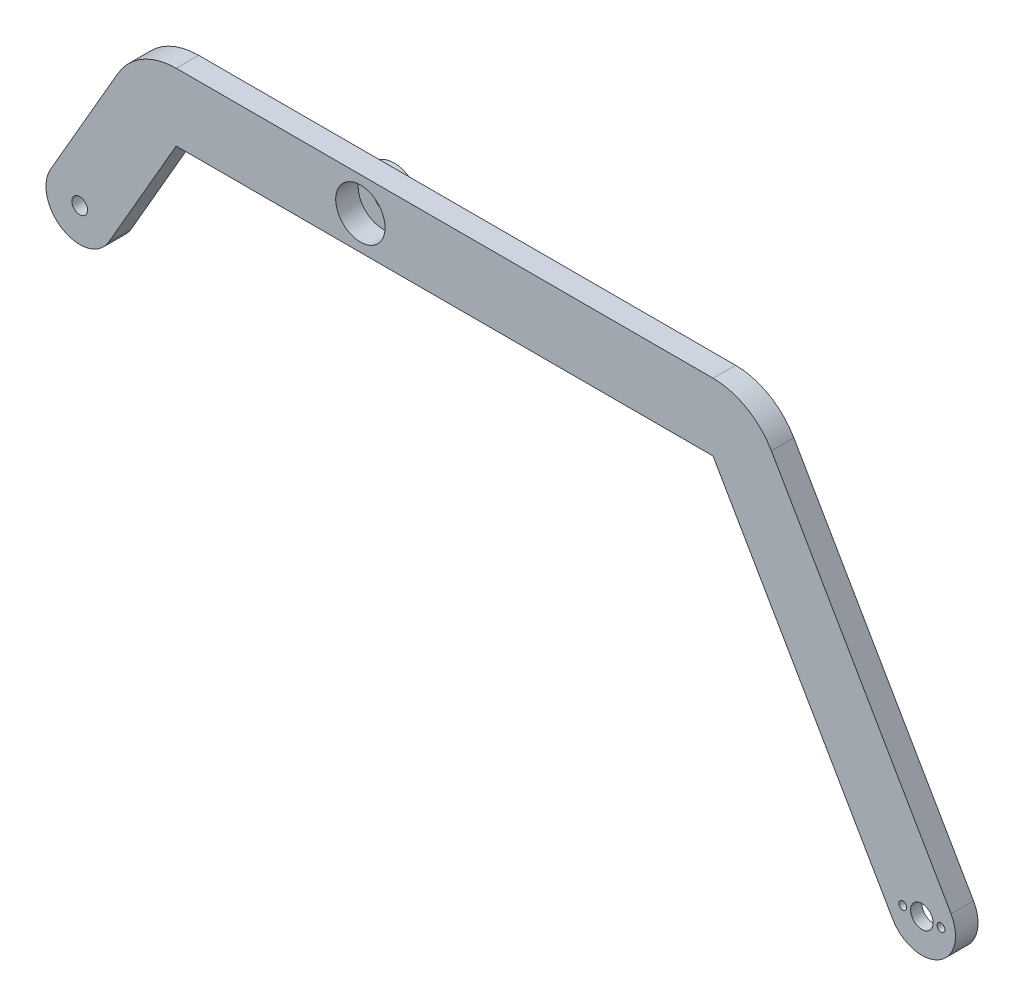
SolidWorks part; units mm, degrees
ref_plane "Front Plane" through (0, 0, 0) normal (0, 0, 1) x (1, 0, 0)
ref_plane "Top Plane" through (0, 0, 0) normal (0, 1, 0) x (1, 0, 0)
ref_plane "Right Plane" through (0, 0, 0) normal (1, 0, 0) x (0, 0, -1)
sketch "Sketch1" plane through (0, 0, 0) normal (0, 0, 1) x (1, 0, 0)
  line L0 (0, -15) -> (0, 15) construction
  line L4 (-82.0096, -15) -> (-112.0096, -66.9615)
  line L6 (-137.9904, -51.9615) -> (-107.9904, 0)
  line L7 (262.9904, -138.5641) -> (182.9904, 0)
  line L9 (157.0096, -15) -> (237.0096, -153.5641)
  line L10 (0, 15) -> (157.0096, 15)
  line L11 (0, -15) -> (157.0096, -15)
  line L12 (0, 15) -> (-82.0096, 15)
  line L13 (0, -15) -> (-82.0096, -15)
  line L14 (237.0096, -153.5641) -> (262.9904, -138.5641) construction
  line L15 (-137.9904, -51.9615) -> (-112.0096, -66.9615) construction
  arc A1 (-107.9904, 0) -> (-82.0096, 15) centre (-82.0096, -15) cw
  arc A2 (182.9904, 0) -> (157.0096, 15) centre (157.0096, -15) ccw
  arc A6 (237.0096, -153.5641) -> (262.9904, -138.5641) centre (250, -146.0641) ccw
  arc A7 (-137.9904, -51.9615) -> (-112.0096, -66.9615) centre (-125, -59.4615) ccw
  circle A8 centre (258.5, -146.0433) radius 1.75
  circle A9 centre (241.5, -146.0848) radius 1.75
  point P4 (0, 0)
  point P7 (0, -15)
  point P20 (0, 15)
  dimension "D2" = 60
  dimension "D6" = 3.5
  dimension "D7" = 3.5
  dimension "D1" = 30
  dimension "D3" = 250
  dimension "D4" = 160
  dimension "D5" = 125
extrude "Boss-Extrude1" add sketch "Sketch1" along normal blind 10
sketch "Sketch2" plane through (0, 0, 10) normal (0, 0, 1) x (1, 0, 0)
  circle A1 centre (250, -146.0641) radius 5
  circle A2 centre (0, 0) radius 11
  dimension "D1" = 22
extrude "Cut-Extrude1" cut sketch "Sketch2" against normal up to surface (10 mm away) up to face at (260.25, -146.0433, 0)
sketch "Sketch3" plane through (0, 0, 0) normal (0, 0, -1) x (-1, 0, 0)
  circle A0 centre (0, 0) radius 12
extrude "Boss-Extrude2" add sketch "Sketch3" along normal blind 5
sketch "Sketch4" plane through (0, 0, 0) normal (0, 0, -1) x (-1, 0, 0)
  circle A0 centre (-250, -146.0641) radius 13
  dimension "D1" = 26
extrude "Cut-Extrude2" cut sketch "Sketch4" against normal offset from surface (5 mm away) 5 up to face at (255, -146.0641, 10)
sketch "Sketch5" plane through (0, 0, 0) normal (0, 0, 1) x (1, 0, 0)
  circle A0 centre (0, 0) radius 3.5
  circle A1 centre (-125, -59.4615) radius 3.5
  dimension "D1" = 7
  dimension "D2" = 7
extrude "Cut-Extrude3" cut sketch "Sketch5" against normal through all both and the other way through all
